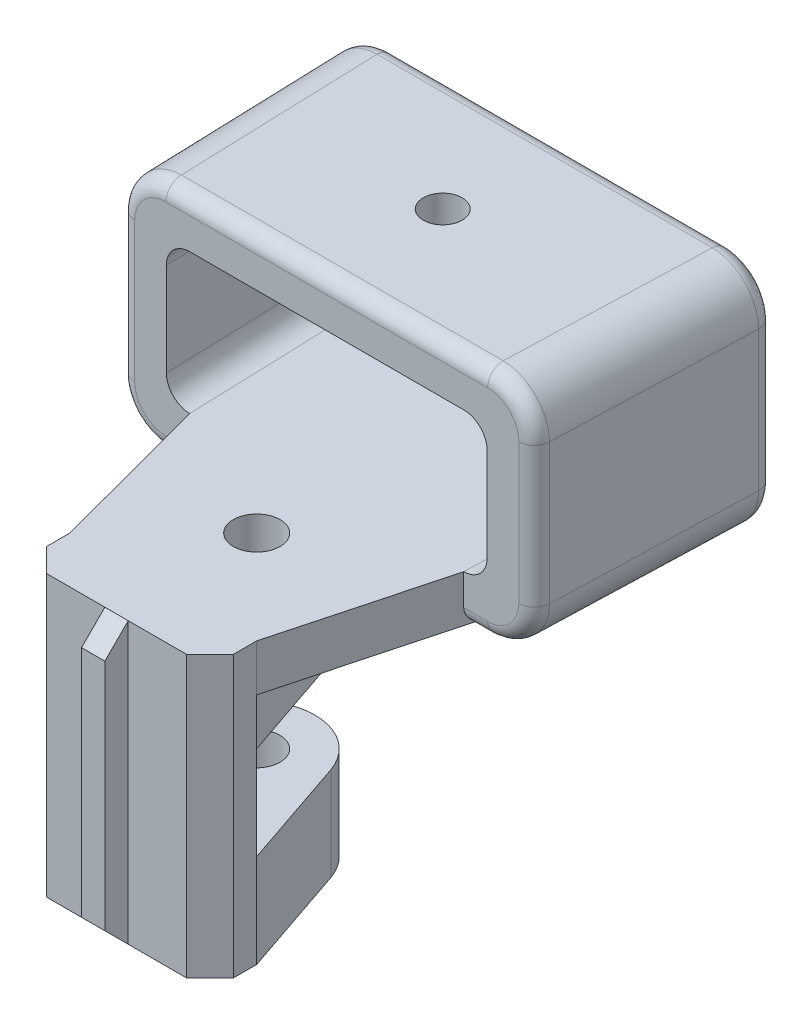
SolidWorks part; units mm, degrees
ref_plane "정면" through (0, 0, 0) normal (0, 0, 1) x (1, 0, 0)
ref_plane "윗면" through (0, 0, 0) normal (0, 1, 0) x (1, 0, 0)
ref_plane "우측면" through (0, 0, 0) normal (1, 0, 0) x (0, 0, -1)
sketch "스케치1" plane through (0, 0, 0) normal (0, 1, 0) x (1, 0, 0)
  line L0 (-12, -12) -> (12, -12)
  line L1 (12, -12) -> (7.101, 2.4135)
  line L2 (-12, -12) -> (-7.101, 2.4135)
  circle A0 centre (0, 0) radius 3
  arc A1 (7.101, 2.4135) -> (-7.101, 2.4135) centre (0, 0) ccw
  point P6 (0, 0)
  point P9 (0, -12)
  dimension "D1" = 6
  dimension "D2" = 15
  dimension "D3" = 24
  dimension "D4" = 12
extrude "보스-돌출1" add sketch "스케치1" along normal blind 12
sketch "스케치2" plane through (0, 0, 0) normal (0, 1, 0) x (1, 0, 0)
  line L0 (-12, -12) -> (12, -12)
  line L1 (12, -12) -> (12, -18)
  line L2 (12, -18) -> (-12, -18)
  line L3 (-12, -18) -> (-12, -12)
  dimension "D1" = 6
extrude "보스-돌출2" add sketch "스케치2" along normal blind 36
sketch "스케치3" plane through (0, 36, 0) normal (0, 1, 0) x (1, 0, 0)
  line L3 (-7.101, 2.4135) -> (-12, -12)
  line L4 (-12, -12) -> (12, -12)
  line L5 (12, -12) -> (7.101, 2.4135)
  line L6 (-7.101, 2.4135) -> (-12, -12)
  line L7 (-12, -12) -> (12, -12)
  line L8 (12, -12) -> (7.101, 2.4135)
  circle A0 centre (0, 0) radius 3 construction
  arc A1 (7.101, 2.4135) -> (-7.101, 2.4135) centre (0, 0) ccw
  arc A2 (7.101, 2.4135) -> (-7.101, 2.4135) centre (0, 0) ccw
  circle A3 centre (0, 0) radius 3
  dimension "D1" = 0
extrude "보스-돌출3" add sketch "스케치3" against normal blind 12
sketch "스케치5" plane through (0, 36, 0) normal (0, 1, 0) x (1, 0, 0)
  line L0 (-20.6, 9) -> (20.6, 9) construction
  line L1 (20.6, 9) -> (21.6, 39)
  line L2 (21.6, 39) -> (-21.6, 39)
  line L3 (-21.6, 39) -> (-20.6, 9)
  line L4 (-20.6, 9) -> (-12, -12)
  line L5 (-12, -12) -> (12, -12)
  line L6 (12, -12) -> (20.6, 9)
  circle A0 centre (0, 0) radius 3 construction
  circle A1 centre (0, 0) radius 3
  point P2 (0, 9)
  point P5 (0, 39)
  dimension "D1" = 41.2
  dimension "D2" = 43.2
  dimension "D3" = 30
  dimension "D4" = 9
extrude "보스-돌출5" add sketch "스케치5" against normal blind 6
sketch "스케치8" plane through (0, 30, 0) normal (0, -1, 0) x (1, 0, 0)
  line L0 (-27.6033, -39) -> (-21.6, -39)
  line L1 (-20.6, -9) -> (-26.6033, -9)
  line L2 (20.6, -9) -> (26.6033, -9)
  line L5 (26.5967, -8.8001) -> (27.5967, -38.8001)
  line L6 (26.6033, -9) -> (27.6033, -39)
  line L7 (-20.6, -9) -> (-21.6, -39)
  line L8 (-27.5967, -38.8001) -> (-26.5967, -8.8001)
  line L9 (-27.6033, -39) -> (-26.6033, -9)
  line L10 (21.6, -39) -> (20.6, -9)
  line L11 (21.6, -39) -> (27.6033, -39)
  point P9 (0, 0)
  point P10 (0, 0)
  dimension "D1" = 6
  dimension "D2" = 6
extrude "보스-돌출7" add sketch "스케치8" against normal blind 30
sketch "스케치9" plane through (0, 0, 0) normal (1, 0, 0) x (0, 0, -1)
  line L0 (33.7, 30) -> (6.7, 25)
  line L1 (39, 30) -> (9, 30) construction
  line L2 (6.7, 25) -> (6.7, 30)
  line L3 (2.4135, 30) -> (7.5, 30) construction
  line L4 (6.7, 30) -> (33.7, 30)
  dimension "D1" = 27
  dimension "D2" = 5
  dimension "D3" = 6.7
extrude "보스-돌출8" add sketch "스케치9" along normal mid plane 6
sketch "스케치10" plane through (0, 60, 0) normal (0, 1, 0) x (1, 0, 0)
  line L0 (20.6, 9) -> (21.6, 39) construction
  line L2 (20.6, 9) -> (21.6, 39)
  line L4 (-21.7, 39) -> (21.6, 39)
  line L6 (-20.6, 9) -> (20.6, 9)
  line L7 (-21.7, 39) -> (-20.6, 9)
  circle A0 centre (-0.1013, 24) radius 2.5
  point P6 (0, 0)
  dimension "D1" = 5
  dimension "D2" = 15
extrude "보스-돌출9" add sketch "스케치10" against normal blind 6
fillet "필렛1" radius 3 4 edges at (-21.1, 54, -24) (-21.1, 36, -24) (21.1, 36, -24) (21.1, 54, -24)
fillet "필렛2" radius 6 4 edges at (-27.1033, 60, -24) (-27.1033, 30, -24) (27.1033, 30, -24) (27.1033, 60, -24)
sketch "스케치11" plane through (0, 0, 0) normal (1, 0, 0) x (0, 0, -1)
  line L0 (-12, 24) -> (-12, 12)
  line L1 (-12, 12) -> (-9, 12)
  line L2 (-9, 12) -> (-9, 24)
  line L3 (-12, 24) -> (2.4135, 24) construction
  line L4 (-9, 24) -> (-12, 24)
  line L5 (-18, 36) -> (-18, 0)
  line L6 (-18, 0) -> (-21, 3)
  line L7 (-21, 3) -> (-21, 33)
  line L8 (-21, 33) -> (-18, 36)
  dimension "D1" = 3
  dimension "D2" = 3
  dimension "D3" = 3
  dimension "D4" = 3
extrude "보스-돌출10" add sketch "스케치11" along normal mid plane 3
sketch "스케치12" plane through (0, 0, -9) normal (0, 0, 1) x (1, 0, 0)
  line L0 (-38.0438, 36) -> (35.8108, 36)
  line L1 (35.8108, 36) -> (35.8108, 40.7102)
  line L2 (35.8108, 40.7102) -> (-38.0438, 40.7102)
  line L3 (-38.0438, 40.7102) -> (-38.0438, 36)
extrude "컷-돌출1" cut sketch "스케치12" along normal blind 13
sketch "스케치13" plane through (0, 36, 0) normal (0, 1, 0) x (1, 0, 0)
  line L0 (-17.5983, 9) -> (-12, -12)
  line L1 (17.5983, 9) -> (12, -12)
  line L2 (-17.5983, 9) -> (-22.9421, 9)
  line L3 (-26.6033, 9) -> (-20.6, 9) construction
  line L4 (-22.9421, 9) -> (-14.2209, -12)
  line L5 (-14.2209, -12) -> (-12, -12)
  line L6 (12, -12) -> (13.7495, -12)
  line L7 (13.7495, -12) -> (23.6017, 9)
  line L8 (20.6, 9) -> (26.6033, 9) construction
  line L9 (23.6017, 9) -> (17.5983, 9)
extrude "컷-돌출2" cut sketch "스케치13" against normal blind 13
fillet "필렛3" radius 2 17 edges at (19.0992, 30, -9) (24.845, 31.7574, -9) (26.6033, 45, -9) (24.845, 58.2426, -9) (-19.0992, 30, -9) (-24.845, 31.7574, -9) (-26.6033, 45, -9) (-24.845, 58.2426, -9) (-25.845, 58.2426, -39) (-27.6033, 45, -39) (-25.845, 31.7574, -39) (0, 30, -39) (25.845, 31.7574, -39) (27.6033, 45, -39) (25.845, 58.2426, -39) (0, 60, -9) (0, 60, -39)
chamfer "모따기1" distance 3 angle 45 2 edges at (12, 18, 18) (-12, 18, 18)
